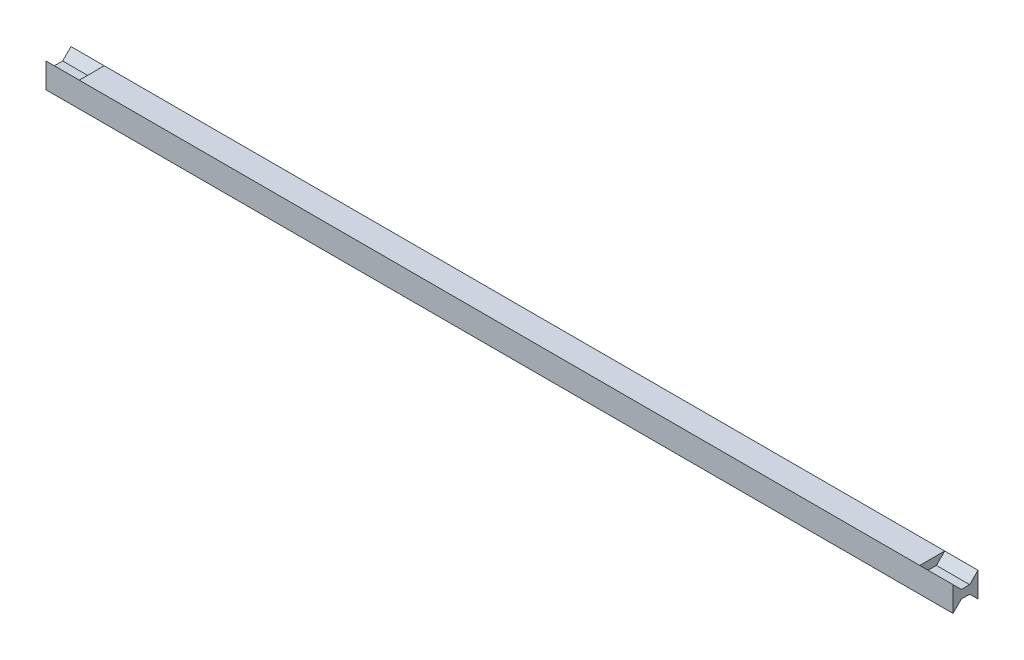
SolidWorks part; units mm, degrees
ref_plane "Přední rovina" through (0, 0, 0) normal (0, 0, 1) x (1, 0, 0)
ref_plane "Horní rovina" through (0, 0, 0) normal (0, 1, 0) x (1, 0, 0)
ref_plane "Pravá rovina" through (0, 0, 0) normal (1, 0, 0) x (0, 0, -1)
sketch "Skica1" plane through (0, 0, 0) normal (0, 1, 0) x (1, 0, 0)
  line L0 (0, 0) -> (202, 0)
  line L1 (202, 0) -> (202, 6)
  line L2 (202, 6) -> (0, 6)
  line L3 (0, 6) -> (0, 0)
  dimension "D1" = 6
  dimension "D2" = 202
extrude "Přidat vysunutím1" add sketch "Skica1" along normal blind 6
sketch "Skica2" plane through (0, 0, 0) normal (-1, 0, 0) x (0, 0, 1)
  line L6 (-6, 6) -> (-6, 0)
  line L7 (-6, 0) -> (-4, 2)
  line L8 (-4, 2) -> (-2, 2)
  line L9 (-2, 2) -> (0, 0)
  line L10 (0, 0) -> (0, 6)
  line L11 (0, 6) -> (-2, 4)
  line L12 (-2, 4) -> (-4, 4)
  line L13 (-4, 4) -> (-6, 6)
  line L14 (0, 0) -> (-6, 0) construction
  line L15 (0, 6) -> (-6, 6) construction
  dimension "D1" = 2
  dimension "D2" = 2
  dimension "D3" = 2
  dimension "D4" = 2
  dimension "D5" = 45
  dimension "D6" = 45
extrude "Přidat vysunutím2" add sketch "Skica2" along normal blind 8
sketch "Skica3" plane through (202, 0, 0) normal (1, 0, 0) x (0, 0, -1)
  line L5 (0, 6) -> (0, 0)
  line L7 (0, 0) -> (2, 2)
  line L8 (2, 2) -> (4, 2)
  line L9 (4, 2) -> (6, 0)
  line L10 (6, 0) -> (6, 6)
  line L11 (6, 6) -> (4, 4)
  line L12 (4, 4) -> (2, 4)
  line L13 (2, 4) -> (0, 6)
  line L14 (0, 0) -> (6, 0) construction
  line L15 (0, 6) -> (6, 6) construction
  dimension "D1" = 2
  dimension "D2" = 2
  dimension "D3" = 2
  dimension "D4" = 2
  dimension "D5" = 45
  dimension "D6" = 45
extrude "Přidat vysunutím3" add sketch "Skica3" along normal blind 8
